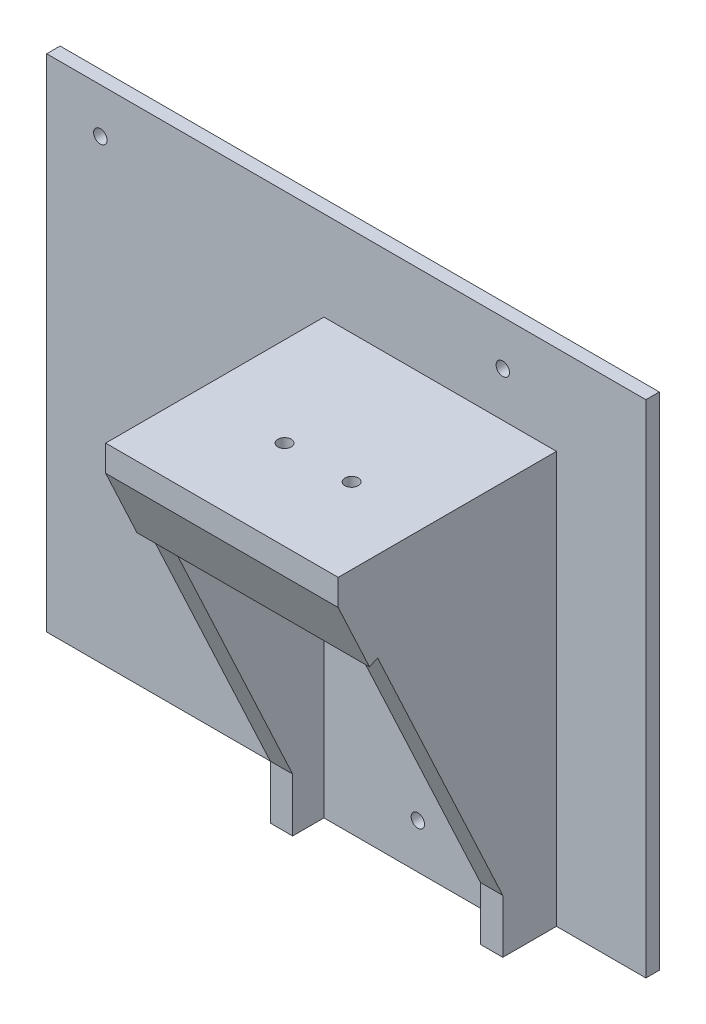
SolidWorks part; units mm, degrees
ref_plane "Alzado" through (0, 0, 0) normal (0, 0, 1) x (1, 0, 0)
ref_plane "Planta" through (0, 0, 0) normal (0, 1, 0) x (1, 0, 0)
ref_plane "Vista lateral" through (0, 0, 0) normal (1, 0, 0) x (0, 0, -1)
sketch "Croquis1" plane through (0, 0, 0) normal (0, 0, 1) x (1, 0, 0)
  line L1 (-67, -56) -> (67, -56)
  line L2 (-67, -56) -> (-67, 56)
  line L3 (-67, 56) -> (67, 56)
  line L4 (67, -56) -> (67, 56)
  line L5 (-67, -56) -> (67, 56) construction
  line L6 (-67, 56) -> (67, -56) construction
  point P0 (0, 0)
  dimension "D1" = 134
  dimension "D2" = 112
extrude "Saliente-Extruir1" add sketch "Croquis1" along normal blind 3
sketch "Croquis2" plane through (0, 0, 3) normal (0, 0, 1) x (1, 0, 0)
  line L0 (-67, -56) -> (-5, -56)
  line L1 (-67, -56) -> (67, -56) construction
  line L2 (-5, -56) -> (-5, 36)
  line L3 (-5, 36) -> (47, 36)
  line L4 (47, 36) -> (47, -56)
  line L5 (47, -56) -> (-5, -56)
  line M9 (-67, -56) -> (67, -56)
  dimension "D1" = 62
  dimension "D2" = 92
  dimension "D3" = 52
extrude "Saliente-Extruir2" add sketch "Croquis2" along normal blind 48.812 contours L4 L3 L2 M9 region at (21, -10, 3)
sketch "Croquis3" plane through (-5, 0, 0) normal (-1, 0, 0) x (0, 0, 1)
  line L0 (3, 36) -> (51.812, 36)
  line L1 (51.812, 36) -> (3, 36) construction
  line L2 (51.812, 36) -> (51.812, 30.154)
  line L3 (51.812, -56) -> (51.812, 36) construction
  line L4 (51.812, 30.154) -> (44.8119, 15.154)
  line L5 (3, -56) -> (15, -56)
  line L6 (51.812, -56) -> (3, -56) construction
  line L7 (15, -56) -> (15, -44)
  line L8 (15, -44) -> (43.0002, 16.0001)
  line L9 (43.0002, 16.0001) -> (44.8119, 15.154)
  line L10 (51.812, 30.154) -> (51.812, -56)
  line L11 (51.812, -56) -> (15, -56)
  line M7 (3, -56) -> (51.812, -56)
  line M8 (51.812, -56) -> (51.812, 36)
  dimension "D1" = 5.846
  dimension "D2" = 16.553
  dimension "D3" = 154.983
  dimension "D4" = 12
  dimension "D5" = 12
  dimension "D6" = 66.212
  dimension "D7" = 154.983
extrude "Cortar-Extruir1" cut sketch "Croquis3" against normal through all contours L9 L8 L7 L4 M7 M8 region at (-5, -26.2329, 37.9141)
shell "Vaciado1" thickness 5 removed face at (21, 22.654, 48.312) removed face at (10.5, -56, 5.25) removed face at (21, -50, 15) removed face at (21, -13.9999, 29.0001)
sketch "Croquis4" plane through (0, -56, 0) normal (0, -1, 0) x (1, 0, 0)
  line L0 (-5, 3) -> (-5, 8)
  line L1 (-5, 15) -> (-5, 3) construction
  line L2 (-5, 8) -> (47, 8)
  line L3 (47, 15) -> (47, 3) construction
  line L4 (47, 8) -> (47, 3)
  line L5 (47, 3) -> (-5, 3)
  dimension "D1" = 5
extrude "Saliente-Extruir3" add sketch "Croquis4" against normal blind 90
sketch "Croquis5" plane through (0, 0, 8) normal (0, 0, 1) x (1, 0, 0)
  line L0 (21, -56) -> (21, -46) construction
  line L1 (42, -56) -> (0, -56) construction
  line L2 (-67, 56) -> (-67, -56) construction
  line L3 (67, -56) -> (67, 56) construction
  line L4 (67, 56) -> (-67, 56) construction
  circle A0 centre (21, -46) radius 1.5
  circle A1 centre (-55, 46) radius 1.5
  circle A2 centre (35, 46) radius 1.5
  dimension "D2" = 3
  dimension "D4" = 10
  dimension "D5" = 32
  dimension "D1" = 10
  dimension "D3" = 12
  dimension "D6" = 10
extrude "Cortar-Extruir2" cut sketch "Croquis5" against normal blind 90
sketch "Croquis6" plane through (0, 36, 0) normal (0, 1, 0) x (1, 0, 0)
  line L0 (47, -51.812) -> (47, -3) construction
  line L1 (-5, -51.812) -> (47, -51.812) construction
  circle A0 centre (30, -31.812) radius 1.5
  circle A1 centre (15, -31.812) radius 1.5
  dimension "D1" = 17
  dimension "D2" = 15
  dimension "D3" = 3
  dimension "D4" = 3
  dimension "D5" = 20
extrude "Cortar-Extruir3" cut sketch "Croquis6" against normal blind 90
